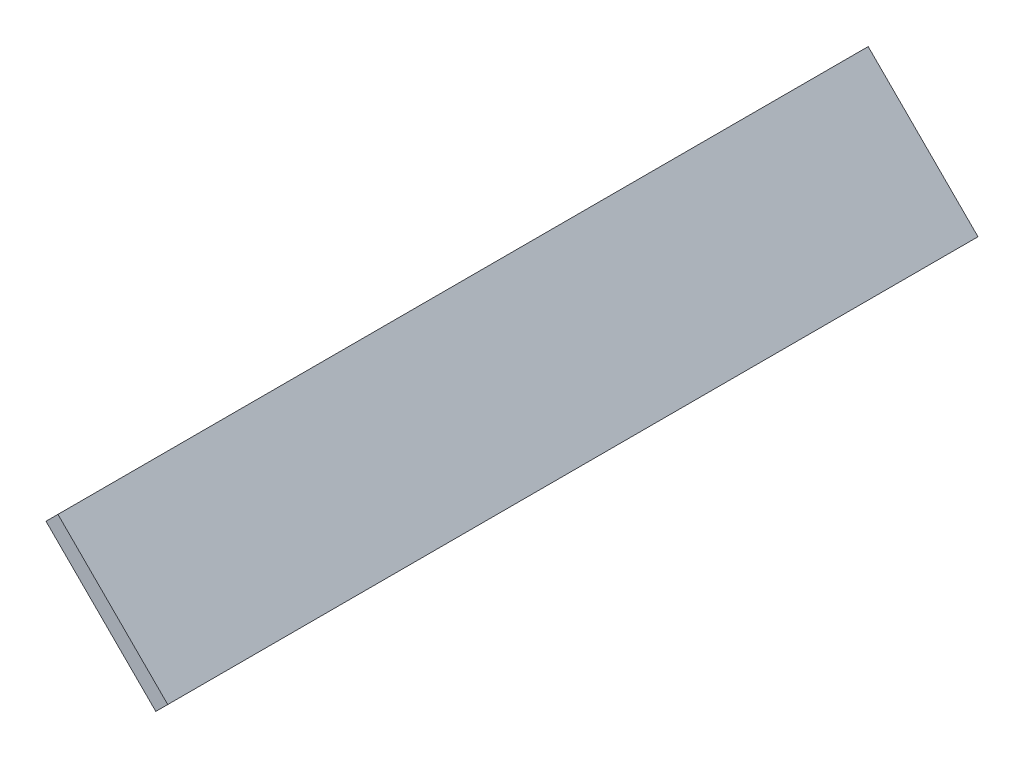
SolidWorks part; units mm, degrees
ref_plane "Front Plane" through (0, 0, 0) normal (0, 0, 1) x (1, 0, 0)
ref_plane "Top Plane" through (0, 0, 0) normal (0, 1, 0) x (1, 0, 0)
ref_plane "Right Plane" through (0, 0, 0) normal (1, 0, 0) x (0, 0, -1)
sketch "Sketch1" plane through (0, 0, 0) normal (0, 0, 1) x (1, 0, 0)
  line L0 (66.9029, 45.85) -> (108.2121, 4.5408)
  line L1 (66.9029, 45.85) -> (71.393, 50.3401)
  line L2 (108.2121, 4.5408) -> (112.7022, 9.0309)
  line L3 (71.393, 50.3401) -> (112.7022, 9.0309)
  line L4 (76.7812, -26.8901) -> (72.2911, -22.4) construction
extrude "Boss-Extrude1" add sketch "Sketch1" along normal up to surface (304.8 mm away)
